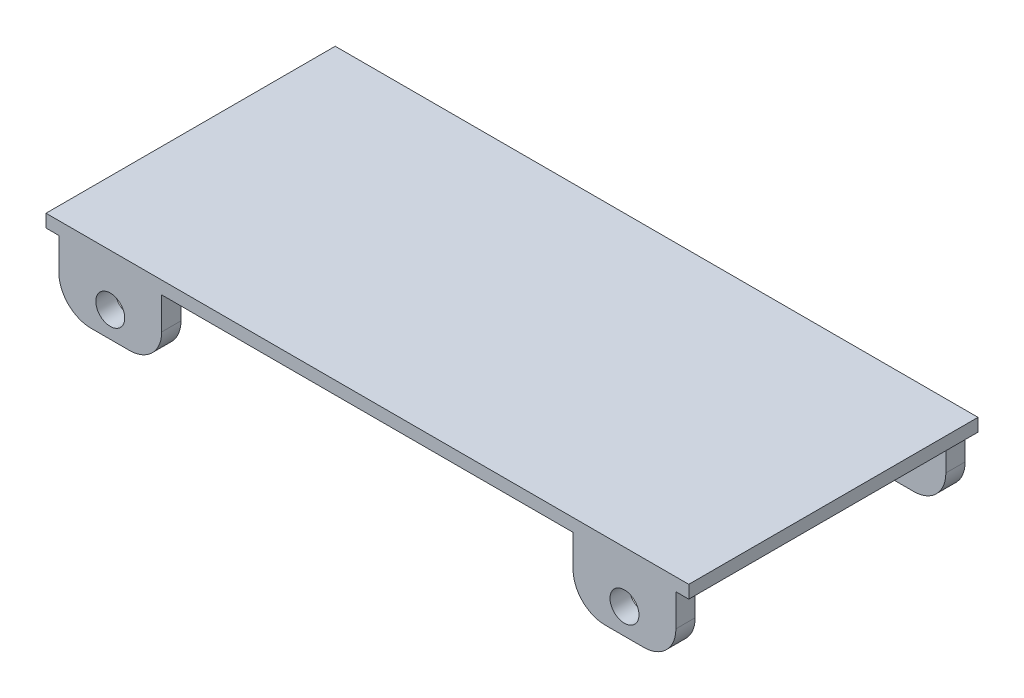
SolidWorks part; units mm, degrees
ref_plane "前视基准面" through (0, 0, 0) normal (0, 0, 1) x (1, 0, 0)
ref_plane "上视基准面" through (0, 0, 0) normal (0, 1, 0) x (1, 0, 0)
ref_plane "右视基准面" through (0, 0, 0) normal (1, 0, 0) x (0, 0, -1)
sketch "草图1" plane through (0, 0, 0) normal (0, 1, 0) x (1, 0, 0)
  line L1 (0, 0) -> (100, 0)
  line L2 (0, 0) -> (0, -45)
  line L3 (0, -45) -> (100, -45)
  line L4 (100, 0) -> (100, -45)
  dimension "D1" = 100
  dimension "D2" = 45
extrude "凸台-拉伸1" add sketch "草图1" along normal blind 2
sketch "草图2" plane through (0, 0, 0) normal (0, -1, 0) x (-1, 0, 0)
  line L0 (0, -45) -> (-100, -45) construction
  line L1 (-2, -45) -> (-18, -45)
  line L2 (-2, -45) -> (-2, -42)
  line L3 (-2, -42) -> (-18, -42)
  line L4 (-18, -45) -> (-18, -42)
  line L5 (0, 0) -> (0, -45) construction
  line L6 (-100, 0) -> (0, 0) construction
  line L7 (-2, 0) -> (-18, 0)
  line L8 (-2, 0) -> (-2, -3)
  line L9 (-2, -3) -> (-18, -3)
  line L10 (-18, 0) -> (-18, -3)
  line L11 (-100, -45) -> (-100, 0) construction
  line L12 (-82, -45) -> (-98, -45)
  line L13 (-82, -45) -> (-82, -42)
  line L14 (-82, -42) -> (-98, -42)
  line L15 (-98, -45) -> (-98, -42)
  line L16 (-82, 0) -> (-98, 0)
  line L17 (-82, 0) -> (-82, -3)
  line L18 (-82, -3) -> (-98, -3)
  line L19 (-98, 0) -> (-98, -3)
  dimension "D1" = 16
  dimension "D2" = 3
  dimension "D3" = 2
  dimension "D4" = 16
  dimension "D5" = 3
  dimension "D6" = 16
  dimension "D7" = 3
  dimension "D8" = 16
  dimension "D9" = 3
  dimension "D10" = 2
  dimension "D11" = 2
  dimension "D12" = 2
extrude "凸台-拉伸2" add sketch "草图2" along normal blind 10
sketch "草图3" plane through (0, 0, 45) normal (0, 0, 1) x (1, 0, 0)
  line L0 (98, -10) -> (82, -10) construction
  line L1 (18, -10) -> (2, -10) construction
  circle A0 centre (90, -6) radius 2.25
  circle A1 centre (10, -6) radius 2.25
  dimension "D1" = 4.5
  dimension "D2" = 4.5
  dimension "D3" = 4
  dimension "D4" = 4
extrude "切除-拉伸1" cut sketch "草图3" against normal through all
sketch "草图4" plane through (0, 0, 0) normal (0, -1, 0) x (-1, 0, 0)
  line L0 (-18, -45) -> (-82, -45) construction
  line L1 (-70, -20) -> (-75, -20)
  line L2 (-70, -20) -> (-70, -25)
  line L3 (-70, -25) -> (-75, -25)
  line L4 (-75, -20) -> (-75, -25)
  line L5 (-82, 0) -> (-18, 0) construction
  line L6 (-100, -45) -> (-100, 0) construction
  dimension "D1" = 25
  dimension "D2" = 25
  dimension "D3" = 5
  dimension "D4" = 30
extrude "凸台-拉伸3" add sketch "草图4" along normal blind 12
sketch "草图5" plane through (0, 0, 25) normal (0, 0, 1) x (1, 0, 0)
  line L1 (75, -9.158) -> (74, -9.158)
  line L2 (75, -9.158) -> (75, -3.9483)
  line L3 (75, -3.9483) -> (74, -3.9483)
  line L4 (74, -9.158) -> (74, -3.9483)
  line L5 (75, -12) -> (75, 0) construction
  dimension "D1" = 0
  dimension "D2" = 1
fillet "圆角1" radius 5 8 edges at (98, -10, 43.5) (82, -10, 43.5) (98, -10, 1.5) (82, -10, 1.5) (18, -10, 1.5) (2, -10, 1.5) (2, -10, 43.5) (18, -10, 43.5)
fillet "圆角2" radius 5 2 edges at (70, -12, 22.5) (70, 0, 22.5)
fillet "圆角3" radius 2 4 edges at (10, 0, 3) (90, 0, 3) (90, 0, 42) (10, 0, 42)
extrude "Cut-Extrude1" cut sketch "草图5" against normal blind 10
